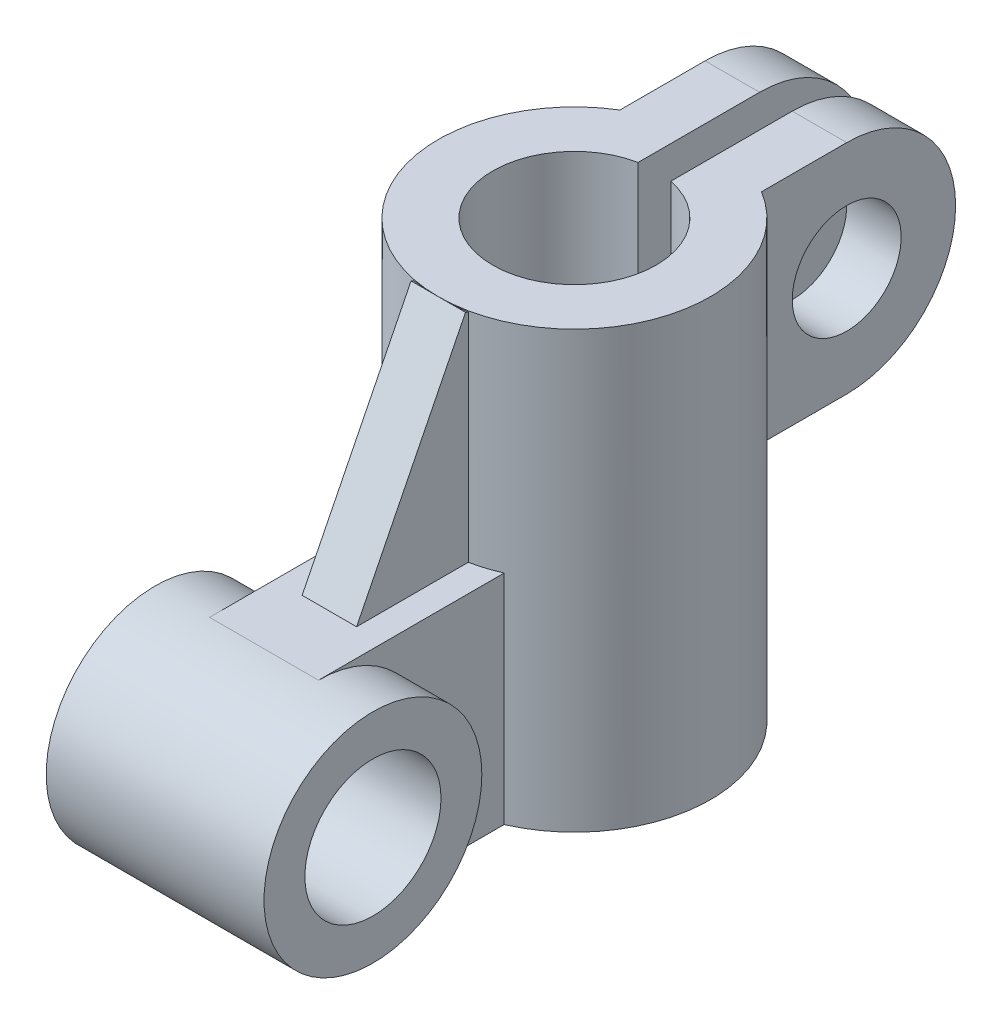
SolidWorks part; units mm, degrees
ref_plane "Front Plane" through (0, 0, 0) normal (0, 0, 1) x (1, 0, 0)
ref_plane "Top Plane" through (0, 0, 0) normal (0, 1, 0) x (1, 0, 0)
ref_plane "Right Plane" through (0, 0, 0) normal (1, 0, 0) x (0, 0, -1)
sketch "Sketch1" plane through (0, 0, 0) normal (0, 1, 0) x (1, 0, 0)
  circle A0 centre (0, 0) radius 25
  circle A1 centre (0, 0) radius 15
  dimension "D1" = 50
  dimension "D2" = 30
extrude "Boss-Extrude1" add sketch "Sketch1" along normal blind 40 and the other way blind 40
sketch "Sketch2" plane through (0, 0, 0) normal (1, 0, 0) x (0, 0, -1)
  line L0 (0, 40) -> (37, 40) construction
  line L1 (25, 40) -> (-25, 40) construction
  line L2 (37, 40) -> (25, 40)
  line L4 (25, 40) -> (25, 0)
  line L5 (37, 0) -> (25, 0)
  line L7 (25, -40) -> (25, 40) construction
  arc A0 (37, 0) -> (37, 40) centre (37, 20) ccw
  circle A1 centre (37, 20) radius 10
  dimension "D3" = 20
  dimension "D1" = 37
  dimension "D2" = 40
extrude "Boss-Extrude2" add sketch "Sketch2" along normal mid plane 26 separate body
sketch "Sketch3" plane through (0, 0, -25) normal (0, 0, 1) x (1, 0, 0)
  line L4 (-13, 40) -> (-13, 0)
  line L5 (-13, 0) -> (13, 0)
  line L6 (13, 0) -> (13, 40)
  line L7 (13, 40) -> (-13, 40)
  line L8 (-13, 40) -> (-13, 0)
  line L9 (-13, 0) -> (13, 0)
  line L10 (13, 0) -> (13, 40)
  line L11 (13, 40) -> (-13, 40)
  dimension "D1" = 0
extrude "Boss-Extrude3" add sketch "Sketch3" along normal up to next (10 mm away)
sketch "Sketch4" plane through (0, 40, 0) normal (0, 1, 0) x (1, 0, 0)
  line L0 (0, 0) -> (0, 75.8786) construction
  line L2 (-3, 151.7572) -> (3, 151.7572)
  line L3 (-3, 151.7572) -> (-3, 0)
  line L4 (-3, 0) -> (3, 0)
  line L5 (3, 151.7572) -> (3, 0)
  line L6 (-3, 151.7572) -> (3, 0) construction
  line L7 (-3, 0) -> (3, 151.7572) construction
  dimension "D1" = 6
extrude "Cut-Extrude1" cut sketch "Sketch4" against normal through all
sketch "Sketch5" plane through (0, -40, 0) normal (0, -1, 0) x (1, 0, 0)
  line L0 (0, 0) -> (0, 45) construction
  line L1 (0, 45) -> (0, 57) construction
  dimension "D1" = 45
  dimension "D2" = 12
sketch "Sketch7" plane through (0, 0, 0) normal (1, 0, 0) x (0, 0, -1)
  line L0 (-25, -40) -> (-57, -40)
  line L1 (-25, -40) -> (-25, 0)
  line L2 (-57, -40) -> (-57, 0)
  line L3 (-25, 0) -> (-57, 0)
  line L5 (-45, -40) -> (-57, -40) construction
  circle A0 centre (-57, -20) radius 20
  circle A1 centre (-57, -20) radius 12.5
  dimension "D1" = 25
  dimension "D2" = 40
extrude "Boss-Extrude4" add sketch "Sketch7" along normal mid plane 20 separate body contours A0 L0 L1 L3 region at (0, -20, 33.7576)
extrude "Boss-Extrude5" add sketch "Sketch7<3>" along normal mid plane 40 contours A0 | A1
sketch "Sketch7<3>" plane through (0, 0, 0) normal (1, 0, 0) x (0, 0, -1) same geometry as "Sketch7"
sketch "Sketch9" plane through (0, 0, 25) normal (0, 0, -1) x (-1, 0, 0)
  line L4 (10, -40) -> (10, 0)
  line L5 (10, 0) -> (-10, 0)
  line L6 (-10, 0) -> (-10, -40)
  line L7 (-10, -40) -> (10, -40)
  line L8 (10, -40) -> (10, 0)
  line L9 (10, 0) -> (-10, 0)
  line L10 (-10, 0) -> (-10, -40)
  line L11 (-10, -40) -> (10, -40)
  dimension "D1" = 0
extrude "Boss-Extrude6" add sketch "Sketch9" along normal up to next (10 mm away)
sketch "Sketch10" plane through (0, 0, 0) normal (0, 1, 0) x (1, 0, 0)
  line L0 (0, 0) -> (0, -45) construction
  line L1 (0, -25) -> (0, -57) construction
  arc A0 (-13, 21.3542) -> (13, 21.3542) centre (0, 0) ccw construction
  arc A1 (-13, 21.3542) -> (13, 21.3542) centre (0, 0) ccw
sketch "Sketch11" plane through (0, 0, 0) normal (1, 0, 0) x (0, 0, -1)
  line L0 (-45, 0) -> (-25, 40)
  line L4 (-45, 0) -> (-45, -2.0005)
  line L5 (-45, -2.0005) -> (-21.6154, -2.0005)
  line L6 (-21.6154, -2.0005) -> (-21.6154, 38.4907)
  line L7 (-21.6154, 38.4907) -> (-25, 40)
  line L8 (-45, -2.0005) -> (-45, 0)
extrude "Boss-Extrude11" add sketch "Sketch11" along normal mid plane 10 contours L6 L7 L0 L4 L5 region at (0, 13.6183, 29.886)
